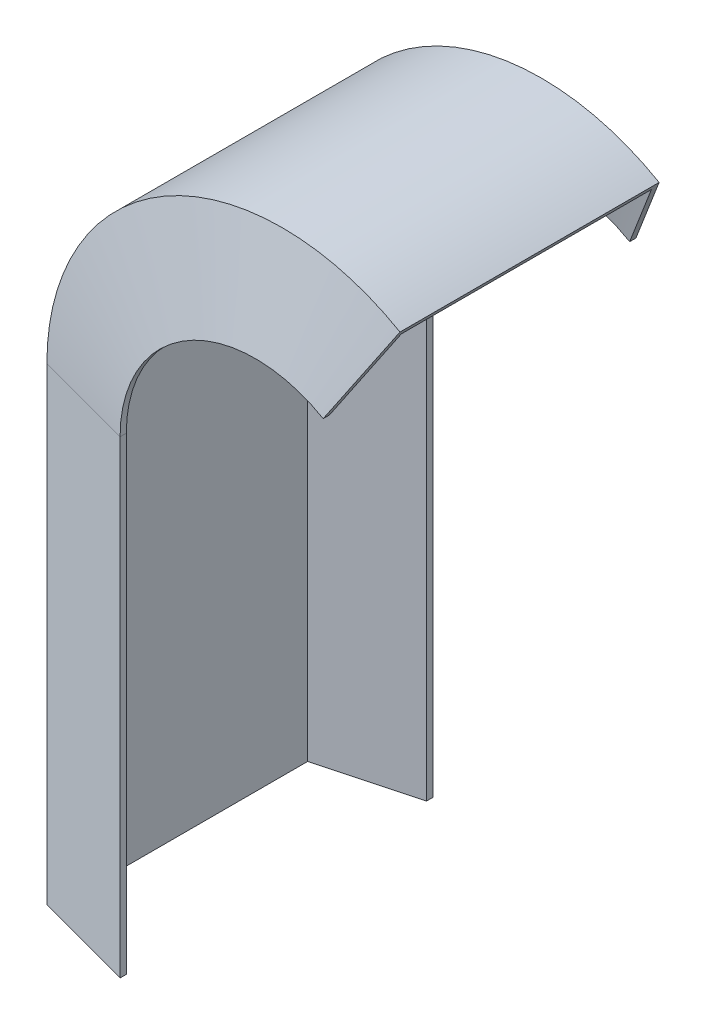
SolidWorks part; units mm, degrees
ref_plane "Front Plane" through (0, 0, 0) normal (0, 0, 1) x (1, 0, 0)
ref_plane "Top Plane" through (0, 0, 0) normal (0, 1, 0) x (1, 0, 0)
ref_plane "Right Plane" through (0, 0, 0) normal (1, 0, 0) x (0, 0, -1)
sketch "Sketch1" plane through (0, 0, 0) normal (0, 0, 1) x (1, 0, 0)
  line L0 (0, 0) -> (0, 150)
  line L1 (110, 213.5085) -> (73.3333, 150) construction
  line L2 (73.3333, 150) -> (73.3333, 223.3333) construction
  arc A0 (0, 150) -> (110, 213.5085) centre (73.3333, 150) cw
  dimension "D3" = 30
  dimension "D1" = 110
  dimension "D2" = 150
sketch "Sketch2" plane through (0, 0, 0) normal (0, 1, 0) x (1, 0, 0)
  line L0 (0, 40) -> (0, -40)
  line L1 (0, -40) -> (30, -48.0385)
  line L2 (30, -48.0385) -> (30, -50.0385)
  line L3 (30, -50.0385) -> (-2, -41.4641)
  line L4 (-2, -41.4641) -> (-2, 41.4641)
  line L5 (-2, 41.4641) -> (30, 50.0385)
  line L6 (30, 50.0385) -> (30, 48.0385)
  line L7 (30, 48.0385) -> (0, 40)
  line L8 (0, 0) -> (-2, 0) construction
  point P2 (30, -149.223)
  point P11 (0, 0)
  point P13 (0, 0)
  point P14 (0, -51.2606)
  dimension "D1" = 105
  dimension "D2" = 80
  dimension "D3" = 30
  dimension "D4" = 2
sweep "Sweep2" add profiles "Sketch2" path "Sketch1"
